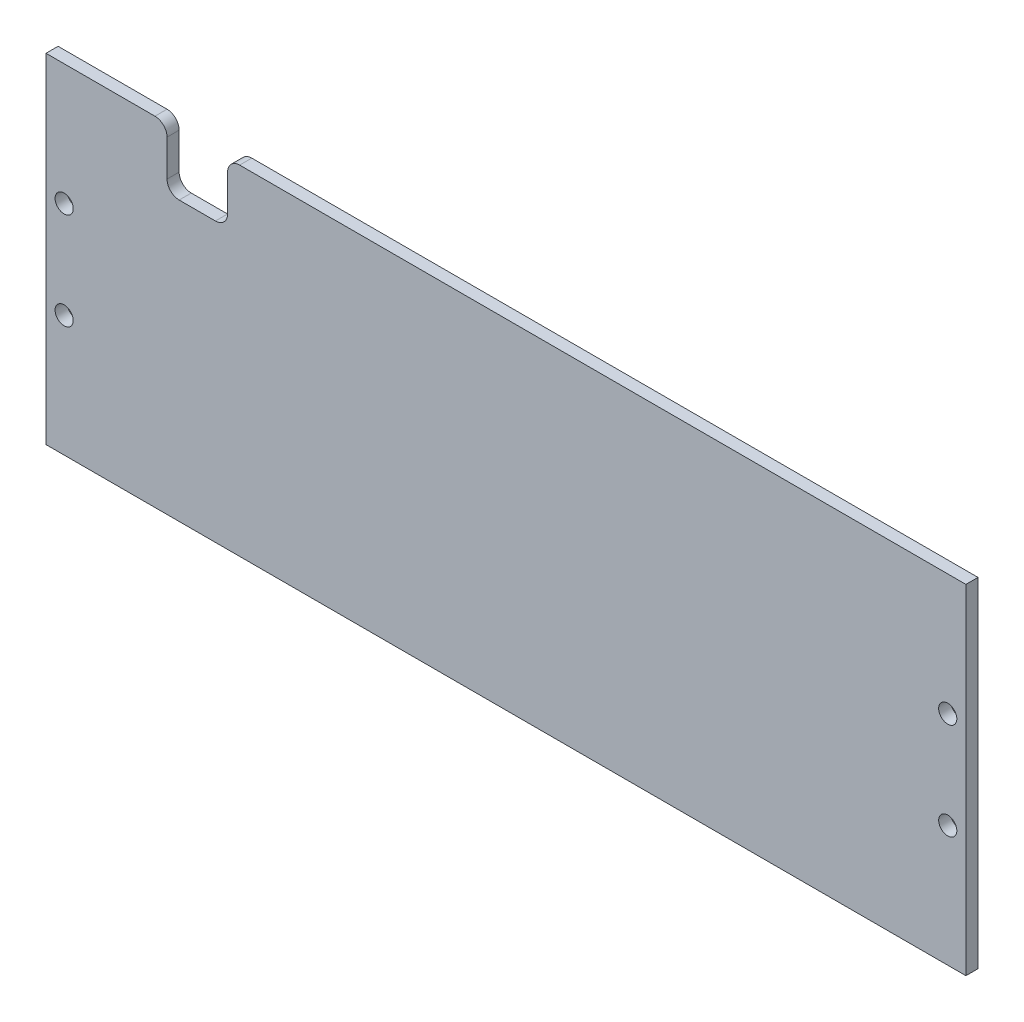
SolidWorks part; units mm, degrees
ref_plane "Plan de face" through (0, 0, 0) normal (0, 0, 1) x (1, 0, 0)
ref_plane "Plan de dessus" through (0, 0, 0) normal (0, 1, 0) x (1, 0, 0)
ref_plane "Plan de droite" through (0, 0, 0) normal (1, 0, 0) x (0, 0, -1)
sketch "Esquisse1" plane through (0, 0, 0) normal (0, 0, 1) x (1, 0, 0)
  line L0 (0, 56) -> (3, 56) construction
  line L1 (0, 0) -> (152, 0)
  line L2 (0, 0) -> (0, 56)
  line L4 (152, 0) -> (152, 56)
  line L5 (3, 56) -> (3, 36) construction
  line L6 (3, 36) -> (3, 20) construction
  line L7 (3, 20) -> (3, 0) construction
  line L8 (152, 56) -> (149, 56) construction
  line L9 (149, 56) -> (149, 36) construction
  line L10 (149, 36) -> (149, 20) construction
  line L11 (149, 20) -> (149, 0) construction
  line L12 (0, 56) -> (152, 56)
  circle A0 centre (3, 36) radius 1.5
  circle A1 centre (3, 20) radius 1.5
  circle A2 centre (149, 20) radius 1.5
  circle A3 centre (149, 36) radius 1.5
  dimension "D4" = 3
  dimension "D1" = 56
  dimension "D2" = 152
  dimension "D3" = 3
  dimension "D5" = 20
extrude "Boss.-Extru.1" add sketch "Esquisse1" along normal blind 2
sketch "Esquisse2" plane through (0, 0, 2) normal (0, 0, 1) x (1, 0, 0)
  line L0 (152, 56) -> (0, 56) construction
  line L1 (20, 56) -> (30, 56)
  line L2 (20, 56) -> (20, 46)
  line L3 (20, 46) -> (30, 46)
  line L4 (30, 56) -> (30, 46)
  line L5 (0, 56) -> (0, 0) construction
  dimension "D1" = 20
  dimension "D2" = 10
extrude "Enlèv. mat.-Extru.1" cut sketch "Esquisse2" against normal through all
fillet "Congé1" radius 2 4 edges at (20, 56, 1) (30, 56, 1) (30, 46, 1) (20, 46, 1)
